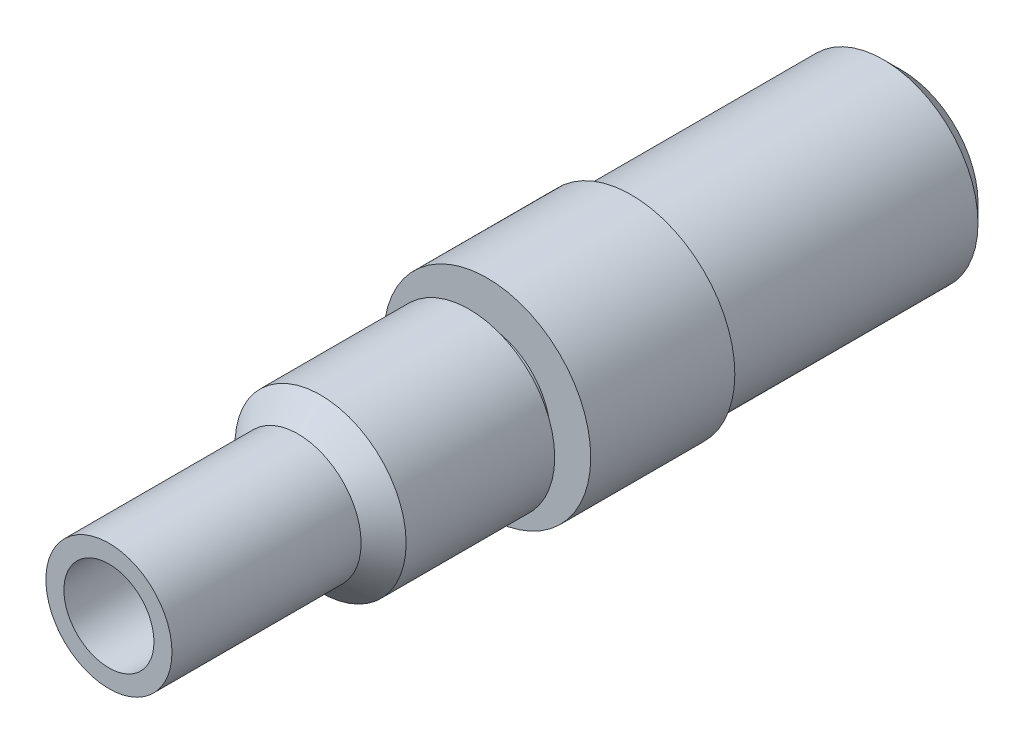
SolidWorks part; units mm, degrees
material "Alliage de zinc AC41A, brut"
ref_plane "Plan de face" through (0, 0, 0) normal (0, 0, 1) x (1, 0, 0)
ref_plane "Plan de dessus" through (0, 0, 0) normal (0, 1, 0) x (1, 0, 0)
ref_plane "Plan de droite" through (0, 0, 0) normal (1, 0, 0) x (0, 0, -1)
sketch "Esquisse1" plane through (0, 0, 0) normal (0, 0, 1) x (1, 0, 0)
  circle A0 centre (0, 0) radius 2.5
  circle A1 centre (0, 0) radius 5.25
  dimension "D1" = 5
  dimension "D2" = 10.5
extrude "Boss.-Extru.1" add sketch "Esquisse1" along normal blind 15
sketch "Esquisse2" plane through (0, 0, 15) normal (0, 0, 1) x (1, 0, 0)
  circle A0 centre (0, 0) radius 2.5
  circle A1 centre (0, 0) radius 5.75
  dimension "D1" = 5
  dimension "D2" = 11.5
extrude "Boss.-Extru.2" add sketch "Esquisse2" along normal blind 8
sketch "Esquisse3" plane through (0, 0, 23) normal (0, 0, 1) x (1, 0, 0)
  circle A0 centre (0, 0) radius 2.5
  circle A1 centre (0, 0) radius 3.5
  dimension "D1" = 5
  dimension "D2" = 7
extrude "Boss.-Extru.3" add sketch "Esquisse3" along normal blind 1
sketch "Esquisse4" plane through (0, 0, 24) normal (0, 0, 1) x (1, 0, 0)
  circle A0 centre (0, 0) radius 4.75
  circle A1 centre (0, 0) radius 2.5
  dimension "D1" = 9.5
  dimension "D2" = 5
extrude "Boss.-Extru.4" add sketch "Esquisse4" along normal blind 8.25
cosmetic thread "Représentation de filetage1" parameters "D2"=8
sketch "Esquisse5" plane through (0, 0, 32.25) normal (0, 0, 1) x (1, 0, 0)
  circle A0 centre (0, 0) radius 2.5
  circle A1 centre (0, 0) radius 3.5
  dimension "D1" = 5
  dimension "D2" = 7
extrude "Boss.-Extru.5" add sketch "Esquisse5" along normal blind 11.75
chamfer "Chanfrein1" distance 1.25 angle 45 1 edges at (3.5, 0, 32.25)
chamfer "Chanfrein2" distance 1 angle 45 1 edges at (5.25, 0, 0)
